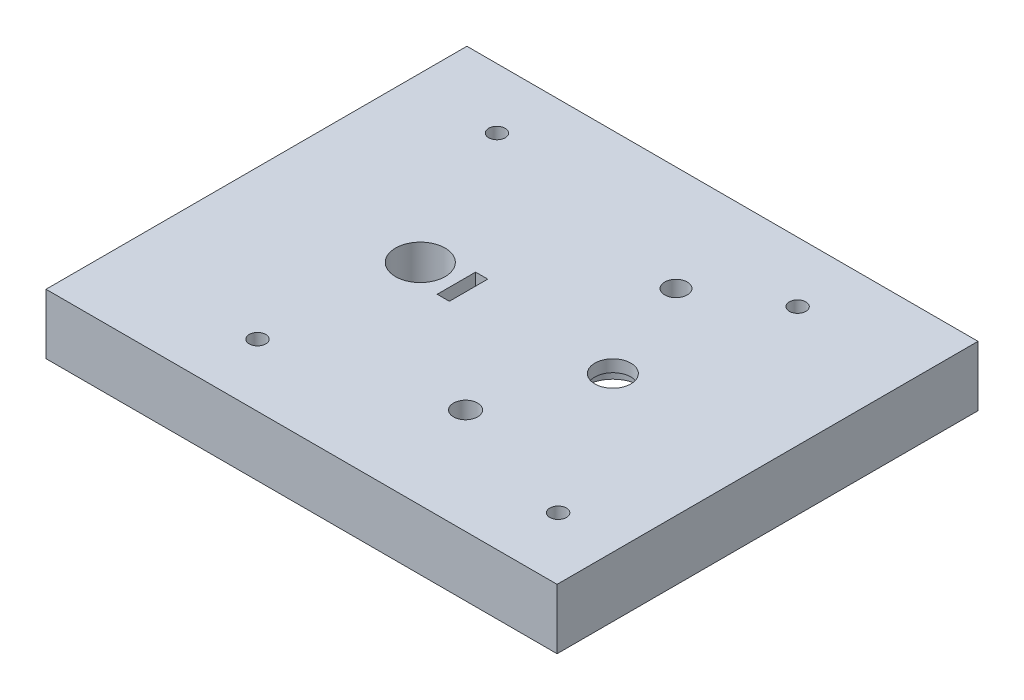
SolidWorks part; units mm, degrees
ref_plane "Front Plane" through (0, 0, 0) normal (0, 0, 1) x (1, 0, 0)
ref_plane "Top Plane" through (0, 0, 0) normal (0, 1, 0) x (1, 0, 0)
ref_plane "Right Plane" through (0, 0, 0) normal (1, 0, 0) x (0, 0, -1)
sketch "Sketch1" plane through (0, 0, 0) normal (0, 1, 0) x (1, 0, 0)
  line L1 (-52.2759, 35) -> (32.7241, 35)
  line L2 (-52.2759, 35) -> (-52.2759, -35)
  line L3 (-52.2759, -35) -> (32.7241, -35)
  line L4 (32.7241, 35) -> (32.7241, -35)
  line L11 (5.5, 2.0001) -> (5.5, -1.9999)
  line L13 (8.5, 2.0001) -> (8.5, -1.9999)
  line L16 (3.625, 17.5) -> (3.625, 13.7295)
  line L17 (-3.625, 17.5) -> (-3.625, 13.7295)
  line L18 (3.625, -17.5) -> (3.625, -13.7295)
  line L19 (-3.625, -17.5) -> (-3.625, -13.7295)
  line L20 (-17, -7) -> (-17, 7)
  line L21 (-17, -7) -> (-12.3548, -7)
  line L22 (-17, 7) -> (-12.3548, 7)
  line L24 (-19.0247, -3.193) -> (-19.0247, 3.193)
  line L25 (-19.0247, 3.193) -> (-17, 3.193)
  line L33 (-19.0247, -3.193) -> (-17, -3.193)
  circle A0 centre (-37.2759, 25) radius 1.375
  circle A1 centre (12.7241, 25) radius 1.375
  circle A2 centre (22.5, -24.6067) radius 1.375
  circle A3 centre (-27.5, -24.6067) radius 1.375
  arc A6 (5.5, 2.0001) -> (8.5, 2.0001) centre (7, 0) cw
  arc A7 (5.5, -1.9999) -> (8.5, -1.9999) centre (7, 0) ccw
  circle A8 centre (7, 0) radius 4.5
  circle A12 centre (-25.0247, 0) radius 4.125
  circle A13 centre (7, 0) radius 3
  arc A14 (-3.625, 13.7295) -> (-12.3548, 7) centre (0, 0) ccw
  circle A17 centre (85.0307, -10.8481) radius 14
  circle A18 centre (86.1334, -28.3481) radius 2
  circle A19 centre (86.1334, 6.6519) radius 2
  arc A20 (-3.625, 13.7295) -> (-12.3548, 7) centre (0, 0) ccw
  circle A21 centre (0, 17.5) radius 1.875
  circle A22 centre (0, -17.5) radius 2
  arc A23 (3.625, 17.5) -> (-3.625, 17.5) centre (0, 17.5) ccw
  arc A24 (-3.625, -17.5) -> (3.625, -17.5) centre (0, -17.5) ccw
  arc A26 (3.625, -13.7295) -> (3.625, 13.7295) centre (0, 0) ccw
  arc A27 (3.625, -13.7295) -> (3.625, 13.7295) centre (0, 0) ccw
  arc A28 (-12.3548, -7) -> (-3.625, -13.7295) centre (0, 0) ccw
  arc A29 (-12.3548, -7) -> (-3.625, -13.7295) centre (0, 0) ccw
  point P0 (0, 0)
  point P5 (0, 0)
  point P9 (0, 0)
  point P10 (0, 0)
  point P11 (-19.0247, 0)
  point P15 (0, 0)
  point P16 (0, 0)
  point P20 (-17, 0)
  point P21 (0, 0)
  point P23 (0, 0)
  point P34 (0, 0)
  point P40 (0, 0)
  point P58 (0, 0)
  point P61 (0, 0)
  point P62 (0, 0)
  point P63 (0, 0)
  point P64 (0, 0)
  point P65 (0, 0)
  point P67 (0, 0)
  point P68 (3.625, 15.6148)
  dimension "D3" = 15
  dimension "D6" = 2.75
  dimension "D7" = 17
  dimension "D10" = 4.6452
  dimension "D11" = 9
  dimension "D12" = 35
  dimension "D13" = 3.75
  dimension "D14" = 6.386
  dimension "D15" = 1.1027
  dimension "D17" = 1.1027
  dimension "D20" = 8.25
  dimension "D21" = 6
  dimension "D16" = 14
  dimension "D25" = 14.2
  dimension "D1" = 85
  dimension "D2" = 70
  dimension "D4" = 10
  dimension "D8" = 4
  dimension "D9" = 3
  dimension "D18" = 2.0247
  dimension "D19" = 4
  dimension "D22" = 32.7241
  dimension "D23" = 6
  dimension "D24" = 7
  dimension "D26" = 35
  dimension "D27" = 17.5
  dimension "D31" = 7.25
  dimension "D32" = 7.25
  dimension "D5" = 2
extrude "Boss-Extrude4" add sketch "Sketch1" along normal blind 10 contours L4 L1 L2 L3 A14 A2 A1 A0 A3 | A14 | A14 | A14 | A14 | A14 A8 | A8 A13 | A14 | L16 A23 L17 A14 A20 A21 | L19 A24 L18 A14 A22 region at (-9.7759, 0, -33.8989) region at (-1.7092, 0, -0.0389) region at (2.6273, 0, 0)
extrude "Cut-Extrude2" cut sketch "Sketch1<7>" along normal blind 6 contours L24 L33 L20 L25 | L21 A28 L19 A24 L18 A26 L16 A23 L17 A14 L22 L20 A8 A21 A22 region at (-1.7092, 0, -0.0389) region at (-18.0123, 0, 0)
sketch "Sketch1<7>" plane through (0, 0, 0) normal (0, 1, 0) x (1, 0, 0) same geometry as "Sketch1"
extrude "Cut-Extrude10" cut sketch "Sketch1<11>" along normal blind 8 contours A8 A13 region at (2.6273, 0, 0)
sketch "Sketch1<11>" plane through (0, 0, 0) normal (0, 1, 0) x (1, 0, 0) same geometry as "Sketch1"
